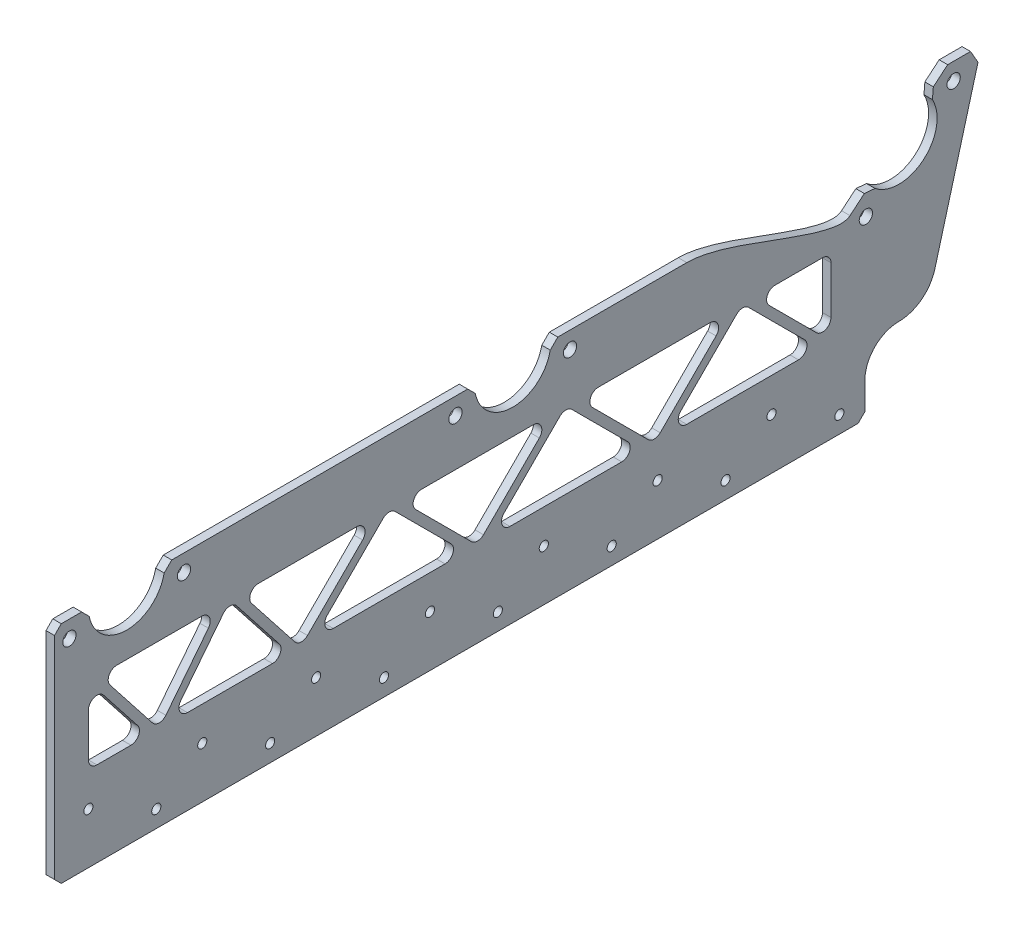
SolidWorks part; units mm, degrees
material "6061 Alloy"
ref_plane "Front Plane" through (0, 0, 0) normal (0, 0, 1) x (1, 0, 0)
ref_plane "Top Plane" through (0, 0, 0) normal (0, 1, 0) x (1, 0, 0)
ref_plane "Right Plane" through (0, 0, 0) normal (1, 0, 0) x (0, 0, -1)
sketch "Sketch1" plane through (0, 0, 0) normal (1, 0, 0) x (0, 0, -1)
  line L0 (-12.7, -12.7) -> (-315.9379, -12.7)
  line L1 (-315.9379, -12.7) -> (-315.9379, 71.4629)
  line L2 (-315.9379, 71.4629) -> (-303.2379, 71.4629)
  line L3 (-274.6121, 71.4629) -> (-158.7754, 71.4629)
  line L5 (10.9643, 80.6631) -> (18.2626, 86.7871)
  line L7 (-315.9379, 12.7) -> (13.4731, 12.7) construction
  line L8 (-12.7, -12.7) -> (-12.7, 0)
  line L9 (0, 12.4079) -> (0, 12.7) construction
  line L10 (13.4731, 22.9772) -> (30.9626, 86.7871)
  line L12 (-10.9643, 62.2627) -> (10.9643, 80.6631) construction
  line L13 (18.2626, 86.7871) -> (30.9626, 86.7871)
  line L14 (-130.1496, 71.4629) -> (-79.3496, 71.4629)
  line L15 (-10.9643, 62.2627) -> (-18.2626, 56.1387)
  line L16 (-315.9379, 15.875) -> (13.4731, 15.875) construction
  line L17 (-288.925, 71.4629) -> (-144.4625, 71.4629) construction
  line L18 (0, 71.4629) -> (-144.4625, 71.4629) construction
  arc A3 (0, 12.7) -> (13.4731, 22.9772) centre (0, 26.67) ccw
  arc A4 (0, 12.7) -> (-12.7, 0) centre (0, 0) ccw
  circle A5 centre (0, 0) radius 12.4079 construction
  arc A6 (-303.2379, 71.4629) -> (-274.6121, 71.4629) centre (-288.925, 71.4629) ccw
  arc A7 (-158.7754, 71.4629) -> (-130.1496, 71.4629) centre (-144.4625, 71.4629) ccw
  arc A8 (-10.9643, 62.2627) -> (10.9643, 80.6631) centre (0, 71.4629) ccw
  spline S0 degree 3 poles (-18.2626, 56.1387) (-24.7485, 50.6965) (-62.4163, 71.4629) (-79.3496, 71.4629) knots 0 0 0 0 1 1 1 1
  point P4 (-164.319, -12.7)
  dimension "D1" = 25.4
  dimension "D3" = 12.7
  dimension "D5" = 28.6258
  dimension "D6" = 41.275
  dimension "D7" = 13.97
  dimension "D8" = 12.7
  dimension "D10" = 24.8158
  dimension "D13" = 9.5273
  dimension "D14" = 140
  dimension "D15" = 50.8
  dimension "D16" = 50.8
  dimension "D17" = 25.4
  dimension "D2" = 0
  dimension "D4" = 12.7
  dimension "D9" = 12.7
  dimension "D11" = 288.925
  dimension "D12" = 288.925
  dimension "D18" = 3.175
extrude "Boss-Extrude1" add sketch "Sketch1" along normal blind 3.175
hole_wizard "#10 Clearance Hole1" positions "Sketch2" profile "Sketch3" hole size "#10" standard "ANSI Inch" end condition through all
sketch "Sketch2" plane through (3.175, 0, 0) normal (1, 0, 0) x (0, 0, -1)
  line L0 (-310.3562, 65.1129) -> (-267.4937, 65.1129) construction
  line L2 (-165.8938, 65.1129) -> (-123.0312, 65.1129) construction
  line L4 (-12.3356, 52.8228) -> (20.499, 80.3743) construction
  line L6 (-303.2379, 71.4629) -> (-315.9379, 71.4629) construction
  line L7 (-288.925, 65.1129) -> (-288.925, 71.4629) construction
  line L9 (-144.4625, 71.4629) -> (-144.4625, 65.1129) construction
  line L11 (0, 71.4629) -> (4.0817, 66.5985) construction
  line L14 (18.2626, 86.7871) -> (10.9643, 80.6631) construction
  line L15 (18.2626, 86.7871) -> (10.9643, 80.6631) construction
  point P0 (-310.3562, 65.1129)
  point P2 (-267.4937, 65.1129)
  point P4 (-165.8938, 65.1129)
  point P6 (-123.0312, 65.1129)
  point P8 (-12.3356, 52.8228)
  point P10 (20.499, 80.3743)
  dimension "D1" = 42.8625
  dimension "D2" = 6.35
  dimension "D3" = 6.35
sketch "Sketch3" plane through (3.175, 65.1129, 310.3562) normal (0, 1, 0) x (0, 0, -1)
  line L0 (0, 0) -> (0, 3.175)
  line L1 (0, 3.175) -> (2.4892, 3.175)
  line L2 (2.4892, 3.175) -> (2.4892, 0)
  line L5 (2.4892, 0) -> (0, 0)
  line L11 (0, -6.35) -> (0, 107.95) construction
  dimension "Thru Hole Dia." = 4.9784
  dimension "Thru Hole Depth" = 3.175
chamfer "Chamfer1" distance 5.08 angle 45 1 edges at (1.5875, 86.7871, -30.9626) first distance on face at (1.5875, 54.8821, -22.2179)
hole_wizard "1/8 (0.135) Diameter Hole1" positions "Sketch4" profile "Sketch5" hole size "1/8" standard "ANSI Inch"
sketch "Sketch4" plane through (3.175, 0, 0) normal (1, 0, 0) x (0, 0, -1)
  line L0 (-315.9379, -12.7) -> (-12.7, -12.7) construction
  line L1 (-12.7, -12.7) -> (-12.7, 0) construction
  line L2 (-315.9379, 71.4629) -> (-315.9379, -12.7) construction
  point P0 (-22.2504, -6.35)
  point P2 (-47.6504, 6.35)
  point P14 (-64.8483, -6.35)
  point P15 (-90.2483, 6.35)
  point P16 (-107.4462, -6.35)
  point P17 (-132.8462, 6.35)
  point P18 (-150.0441, -6.35)
  point P19 (-175.4442, 6.35)
  point P20 (-192.6421, -6.35)
  point P21 (-218.0421, 6.35)
  point P22 (-235.24, -6.35)
  point P23 (-260.64, 6.35)
  point P24 (-277.8379, -6.35)
  point P25 (-303.2379, 6.35)
  dimension "D1" = 6.35
  dimension "D2" = 9.5504
  dimension "D3" = 12.7
  dimension "D4" = 25.4
  dimension "D6" = 12.7
  dimension "D5" = 7
sketch "Sketch5" plane through (3.175, -6.35, 22.2504) normal (0, 1, 0) x (0, 0, -1)
  line L0 (0, 0) -> (0, 17.5402)
  line L1 (0, 17.5402) -> (1.7145, 16.51)
  line L2 (1.7145, 16.51) -> (1.7145, 0)
  line L5 (1.7145, 0) -> (0, 0)
  line L10 (0, 17.5402) -> (-1.7145, 16.51) construction
  line L11 (0, -6.35) -> (0, 107.95) construction
  dimension "Hole Dia." = 3.429
  dimension "Hole Depth" = 16.51
  dimension "Drill Angle" = 118
sketch "Sketch6" plane through (3.175, 0, 0) normal (1, 0, 0) x (0, 0, -1)
  line L0 (-303.2379, 47.625) -> (-303.2379, 19.05)
  line L1 (-303.2379, 19.05) -> (-280.7929, 19.05)
  line L2 (-280.7929, 19.05) -> (-303.2379, 47.625)
  line L3 (-315.9379, 12.7) -> (-12.7, 12.7) construction
  line L4 (-315.9379, 71.4629) -> (-315.9379, -12.7) construction
  line L5 (-315.9379, -12.7) -> (-12.7, -12.7) construction
  line L6 (-315.9379, 15.875) -> (-12.7, 15.875) construction
  line L7 (-299.2006, 47.625) -> (-276.7555, 19.05)
  line L8 (-276.7555, 19.05) -> (-254.3105, 47.625)
  line L9 (-254.3105, 47.625) -> (-299.2006, 47.625)
  line L10 (-272.7182, 19.05) -> (-250.2731, 47.625)
  line L11 (-250.2731, 47.625) -> (-227.8281, 19.05)
  line L12 (-227.8281, 19.05) -> (-272.7182, 19.05)
  line L13 (-246.2358, 47.625) -> (-223.7908, 19.05)
  line L14 (-223.7908, 19.05) -> (-195.2158, 47.625)
  line L15 (-195.2158, 47.625) -> (-246.2358, 47.625)
  line L16 (-219.3006, 19.05) -> (-190.7256, 47.625)
  line L17 (-190.7256, 47.625) -> (-162.1506, 19.05)
  line L18 (-162.1506, 19.05) -> (-219.3006, 19.05)
  line L19 (-186.2355, 47.625) -> (-157.6605, 19.05)
  line L20 (-157.6605, 19.05) -> (-129.0855, 47.625)
  line L21 (-129.0855, 47.625) -> (-186.2355, 47.625)
  line L22 (-124.5954, 47.625) -> (-153.1704, 19.05)
  line L23 (-153.1704, 19.05) -> (-96.0204, 19.05)
  line L24 (-96.0204, 19.05) -> (-124.5954, 47.625)
  line L25 (-120.1053, 47.625) -> (-91.5303, 19.05)
  line L26 (-91.5303, 19.05) -> (-62.9553, 47.625)
  line L27 (-62.9553, 47.625) -> (-120.1053, 47.625)
  line L28 (-58.4651, 47.625) -> (-87.0401, 19.05)
  line L29 (-87.0401, 19.05) -> (-29.8901, 19.05)
  line L30 (-29.8901, 19.05) -> (-58.4651, 47.625)
  line L31 (-12.7, -12.7) -> (-12.7, 0) construction
  line L32 (-53.975, 47.625) -> (-25.4, 19.05)
  line L33 (-25.4, 19.05) -> (-25.4, 47.625)
  line L34 (-25.4, 47.625) -> (-53.975, 47.625)
  arc A0 (-303.2379, 71.4629) -> (-274.6121, 71.4629) centre (-288.925, 71.4629) ccw construction
  dimension "D15" = 9.525
  dimension "D1" = 25.4
  dimension "D3" = 3.175
  dimension "D4" = 12.7
  dimension "D5" = 3.175
  dimension "D6" = 3.175
  dimension "D7" = 3.175
  dimension "D8" = 3.175
  dimension "D9" = 3.175
  dimension "D10" = 3.175
  dimension "D11" = 3.175
  dimension "D12" = 3.175
  dimension "D13" = 3.175
  dimension "D14" = 12.7
  dimension "D2" = 3.175
extrude "Cut-Extrude1" cut sketch "Sketch6" against normal through all
fillet "Fillet1" radius 3.175 30 edges at (1.5875, 19.05, 25.4) (1.5875, 47.625, 53.975) (1.5875, 47.625, 25.4) (1.5875, 19.05, 162.1506) (1.5875, 19.05, 219.3006) (1.5875, 19.05, 91.5303) (1.5875, 47.625, 120.1053) (1.5875, 47.625, 62.9553) (1.5875, 19.05, 87.0401) (1.5875, 47.625, 58.4651) (1.5875, 19.05, 29.8901) (1.5875, 19.05, 157.6605) (1.5875, 47.625, 186.2355) (1.5875, 47.625, 129.0855) (1.5875, 19.05, 153.1704) (1.5875, 47.625, 124.5954) (1.5875, 19.05, 96.0204) (1.5875, 47.625, 190.7256) (1.5875, 19.05, 223.7908) (1.5875, 47.625, 246.2358) (1.5875, 47.625, 195.2158) (1.5875, 19.05, 227.8281) (1.5875, 19.05, 272.7182) (1.5875, 47.625, 250.2731) (1.5875, 19.05, 276.7555) (1.5875, 47.625, 299.2006) (1.5875, 47.625, 254.3105) (1.5875, 19.05, 303.2379) (1.5875, 19.05, 280.7929) (1.5875, 47.625, 303.2379)
chamfer "Chamfer2" distance 2.54 angle 45 9 edges at (1.5875, -12.7, 12.7) (1.5875, -12.7, 315.9379) (1.5875, 71.4629, 315.9379) (1.5875, 80.6631, -10.9643) (1.5875, 62.2627, 10.9643) (1.5875, 71.4629, 130.1496) (1.5875, 71.4629, 158.7754) (1.5875, 71.4629, 274.6121) (1.5875, 71.4629, 303.2379)
